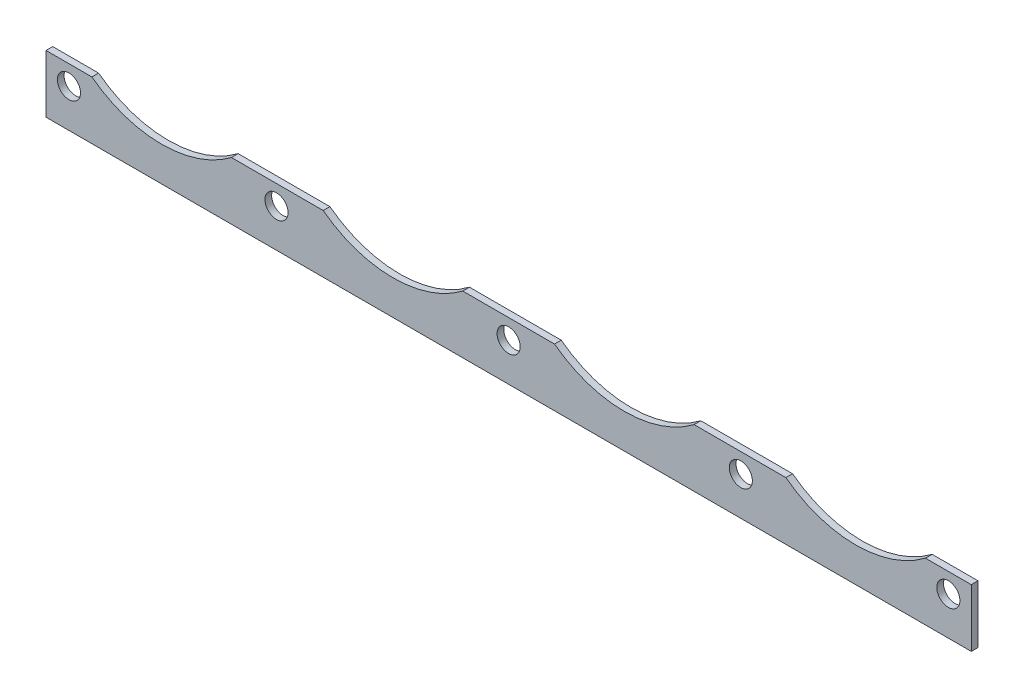
SolidWorks part; units mm, degrees
ref_plane "Front Plane" through (0, 0, 0) normal (0, 0, 1) x (1, 0, 0)
ref_plane "Top Plane" through (0, 0, 0) normal (0, 1, 0) x (1, 0, 0)
ref_plane "Right Plane" through (0, 0, 0) normal (1, 0, 0) x (0, 0, -1)
sketch "Sketch1" plane through (0, 0, 0) normal (0, 0, 1) x (1, 0, 0)
  line L0 (0, 12.7) -> (0, 0) construction
  line L1 (-101.6, 12.7) -> (101.6, 12.7)
  line L2 (-101.6, 12.7) -> (-101.6, 0)
  line L3 (-101.6, 0) -> (101.6, 0)
  line L4 (101.6, 12.7) -> (101.6, 0)
  circle A0 centre (-76.2, 32.9549) radius 25.4
  circle A1 centre (-25.4, 32.9549) radius 25.4
  circle A2 centre (25.4, 32.9549) radius 25.4
  circle A3 centre (76.2, 32.9549) radius 25.4
  circle A4 centre (-96.562, 8.3989) radius 2.54
  circle A5 centre (-50.9847, 8.3989) radius 2.54
  circle A6 centre (96.562, 8.3989) radius 2.54
  circle A7 centre (0, 8.3989) radius 2.54
  circle A8 centre (50.9847, 8.3989) radius 2.54
  dimension "D3" = 50.8
  dimension "D4" = 4
  dimension "D6" = 3
  dimension "D1" = 203.2
  dimension "D2" = 12.7
extrude "Boss-Extrude1" add sketch "Sketch1" along normal mid plane 1.4732 contours L0 L1 A1 A0 L2 L3 A7 A4 A5 | L1 L0 A7 L3 L4 A3 A2 A6 A8 region at (50.3829, 5.3524, 0) region at (-50.3829, 5.3524, 0)
